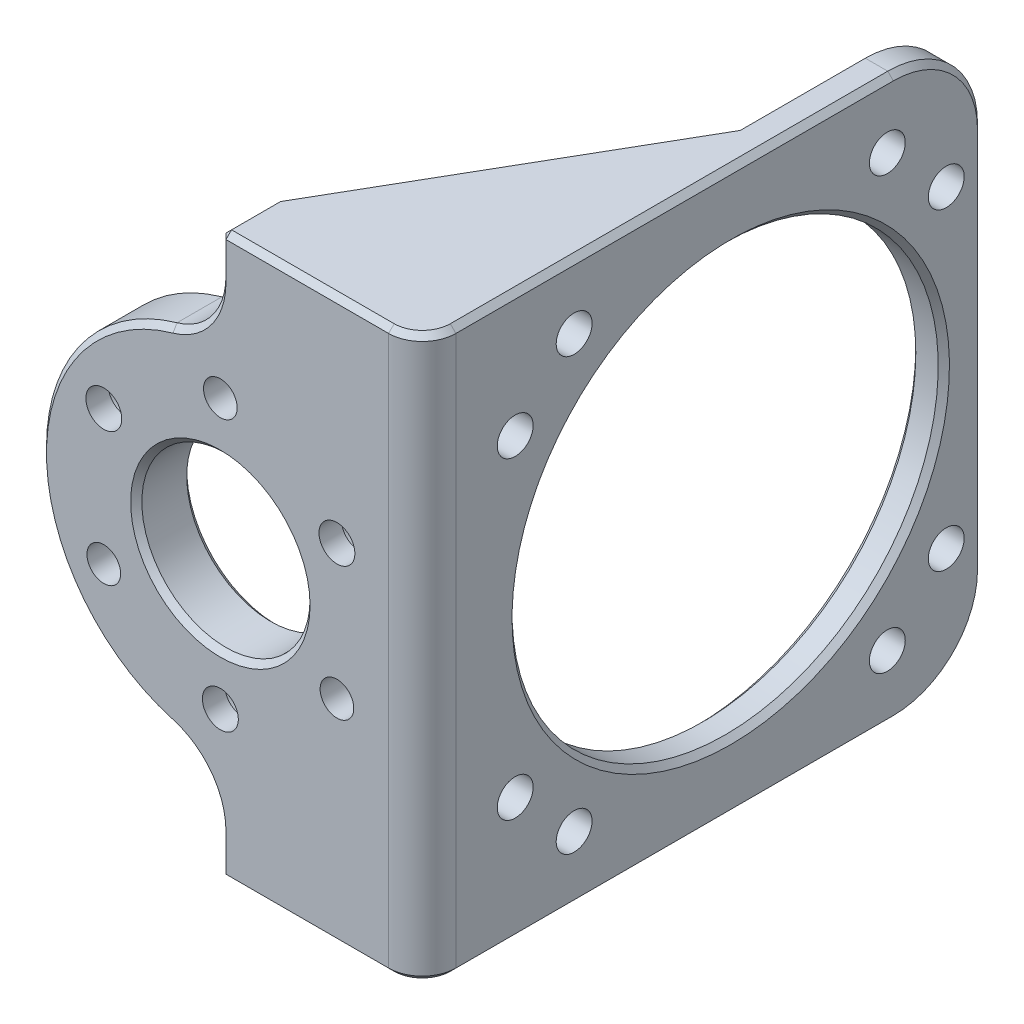
SolidWorks part; units mm, degrees
material "6061 合金"
ref_plane "前视基准面" through (0, 0, 0) normal (0, 0, 1) x (1, 0, 0)
ref_plane "上视基准面" through (0, 0, 0) normal (0, 1, 0) x (1, 0, 0)
ref_plane "右视基准面" through (0, 0, 0) normal (1, 0, 0) x (0, 0, -1)
other "Configuration Table"
sketch "草图1" plane through (0, 0, 0) normal (0, 0, 1) x (1, 0, 0)
  line L0 (-10.7623, 0) -> (8.7048, 0) construction
  line L1 (0, 6.2516) -> (0, -8.3883) construction
  circle A0 centre (0, 0) radius 16
  dimension "D1" = 32
extrude "凸台-拉伸1" add sketch "草图1" along normal blind 5
hole_wizard "Ø3.0mm 暗销孔1" positions "草图3" profile "草图4" hole size "Ø3.0" standard "GB"
sketch "草图3" plane through (0, 0, 5) normal (0, 0, 1) x (1, 0, 0)
  circle A0 centre (0, 0) radius 12 construction
  point P0 (0, 12)
  point P12 (10.3923, -6)
  point P13 (-10.3923, -6)
  dimension "D1" = 24
  dimension "D2" = 3
sketch "草图4" plane through (0, 12, 5) normal (1, 0, 0) x (0, -1, 0)
  line L0 (0, 0) -> (0, 3.9013)
  line L1 (0, 3.9013) -> (1.5, 3)
  line L2 (1.5, 3) -> (1.5, 0)
  line L5 (1.5, 0) -> (0, 0)
  line L10 (0, 3.9013) -> (-1.5, 3) construction
  line L11 (0, -6.35) -> (0, 107.95) construction
  dimension "孔直径" = 3
  dimension "孔深度" = 3
  dimension "导头角度" = 118
hole_wizard "孔1" positions "草图6" profile "草图7" legacy end condition through all
sketch "草图6" plane through (0, 0, 0) normal (0, 0, -1) x (-1, 0, 0)
  circle A0 centre (0, 0) radius 12 construction
  point P0 (0, -12)
  point P13 (-10.3923, 6)
  point P14 (10.3923, 6)
  dimension "D1" = 24
  dimension "D2" = 3
sketch "草图7" plane through (0, -12, 0) normal (1, 0, 0) x (0, 1, 0)
  line L0 (0, 0) -> (0, 5.9614)
  line L1 (0, 5.9614) -> (1.6, 5)
  line L2 (1.6, 5) -> (1.6, 3)
  line L3 (1.6, 3) -> (2.9, 3)
  line L4 (2.9, 0) -> (0, 0)
  line L5 (0, -11.3109) -> (0, 121.1557) construction
  line L6 (0, 5.9614) -> (-1.6, 5) construction
  line L7 (2.9, 3) -> (2.9, 0)
  dimension "直径" = 3.2
  dimension "深度" = 5
  dimension "柱坑直径" = 5.8
  dimension "柱坑深度" = 3
  dimension "导头角度" = 118
sketch "草图8" plane through (0, 0, 0) normal (0, 0, 1) x (1, 0, 0)
  line L0 (37.5243, 0) -> (-36.7763, 0) construction
  line L1 (0, 34.2207) -> (0, -32.974) construction
  line L2 (0, 22) -> (18, 22)
  line L3 (18, 22) -> (18, -22)
  line L4 (18, -22) -> (0, -22)
  line L5 (0, -22) -> (0, -16)
  line L6 (0, 22) -> (0, 16)
  circle A0 centre (0, 0) radius 16 construction
  arc A1 (0, -16) -> (0, 16) centre (0, 0) ccw
  dimension "D1" = 44
  dimension "D2" = 18
extrude "凸台-拉伸2" add sketch "草图8" along normal up to surface (5 mm away) up to face at (-1.6, -12, 5)
sketch "草图9" plane through (0, 0, 0) normal (0, 0, -1) x (-1, 0, 0)
  line L0 (-18, 22) -> (0, 22) construction
  line L1 (-18, -22) -> (-15, -22)
  line L2 (-18, -22) -> (-18, 22)
  line L3 (-18, 22) -> (-15, 22)
  line L4 (-15, -22) -> (-15, 22)
  dimension "D1" = 3
extrude "凸台-拉伸3" add sketch "草图9" along normal blind 45
sketch "草图12" plane through (18, 0, 0) normal (1, 0, 0) x (0, 0, -1)
  line L1 (22.5, 0) -> (41.7142, 13.9599) construction
  line L2 (36.4599, 19.2142) -> (22.3807, -0.1643) construction
  line L3 (-6.3808, 0) -> (22.5, 0) construction
  line L4 (22.5, 0) -> (3.2858, 13.9599) construction
  line L5 (-5, -22) -> (-5, 22) construction
  circle A0 centre (22.5, 0) radius 23.75 construction
  circle A1 centre (3.2858, 13.9599) radius 1.6
  circle A2 centre (36.4599, 19.2142) radius 1.6
  circle A3 centre (41.7142, -13.9599) radius 1.6
  circle A4 centre (8.5401, -19.2142) radius 1.6
  circle A5 centre (41.7142, 13.9599) radius 1.6
  circle A6 centre (36.4599, -19.2142) radius 1.6
  circle A7 centre (3.2858, -13.9599) radius 1.6
  circle A8 centre (8.5401, 19.2142) radius 1.6
  point P22 (22.5, 0)
  point P27 (22.5, 0)
  dimension "D2" = 47.5
  dimension "D4" = 3.2
  dimension "D1" = 27.5
  dimension "D3" = 36
  dimension "D6" = 18
  dimension "D5" = 4
  dimension "D7" = 4
extrude "切除-拉伸1" cut sketch "草图12" against normal blind 45
sketch "草图14" plane through (18, 0, 0) normal (1, 0, 0) x (0, 0, -1)
  circle A0 centre (22.5, 0) radius 19
  dimension "D1" = 38
extrude "切除-拉伸2" cut sketch "草图14" against normal through all
fillet "圆角3" radius 6 2 edges at (0, -16, 2.5) (0, 16, 2.5)
sketch "草图18" plane through (0, 0, 5) normal (0, 0, 1) x (1, 0, 0)
  circle A0 centre (0, 0) radius 7.5
  dimension "D1" = 15
extrude "切除-拉伸4" cut sketch "草图18" against normal through all
sketch "草图21" plane through (0, 22, 0) normal (0, 1, 0) x (1, 0, 0)
  line L1 (15, 45) -> (15, 25.9808)
  line L2 (15, 45) -> (15, 0) construction
  line L3 (15, 25.9808) -> (0, 0)
  line L4 (15, 0) -> (0, 0) construction
  line L6 (0, -5) -> (18, -5)
  line L7 (18, -5) -> (18, 45)
  line L8 (18, 45) -> (15, 45)
  line L9 (15, 45) -> (15, 0)
  line L10 (15, 0) -> (0, 0)
  line L11 (0, 0) -> (0, -5)
  line L12 (0, -5) -> (18, -5)
  line L13 (18, -5) -> (18, 45)
  line L14 (18, 45) -> (15, 45)
  line L17 (0, 0) -> (0, -5)
  dimension "D2" = 60
  dimension "D1" = 0
extrude "凸台-拉伸4" add sketch "草图21" along normal blind 3
mirror "镜向1" about plane through (0, 0, 0) normal (0, 1, 0) of "凸台-拉伸4"
fillet "圆角4" radius 3 1 edges at (18, 0, 5)
fillet "圆角6" radius 8 2 edges at (16.5, -25, -45) (16.5, 25, -45)
chamfer "倒角1" distance 0.5 angle 45 32 edges at (7.5, 0, 0) (7.5, 0, 5) (15, 0, -41.5) (18, 19, -22.5) (0, -25, 2.5) (7.5, -25, -12.9904) (0, -23.083, 5) (-1.2137, -17.5479, 5) (0, 23.083, 5) (-16, 0, 5) (-1.2137, 17.5479, 5) (0, -21.583, 0) (-1.2137, -17.5479, 0) (-16, 0, 0) (0, 21.583, 0) (-1.2137, 17.5479, 0) (7.5, 25, -12.9904) (15, -25, -31.4904) (15, 25, -31.4904) (15, -22.6569, -42.6569) (15, 22.6569, -42.6569) (15, 0, -45) (7.5, 25, 5) (7.5, -25, 5) (17.1213, 25, 4.1213) (17.1213, -25, 4.1213) (18, 25, -17.5) (18, -25, -17.5) (18, 22.6569, -42.6569) (18, -22.6569, -42.6569) (18, 0, -45) (0, 25, 2.5)
chamfer "倒角2" distance 0.5 angle 45 2 edges at (7.5, 22, -12.9904) (7.5, -22, -12.9904)
